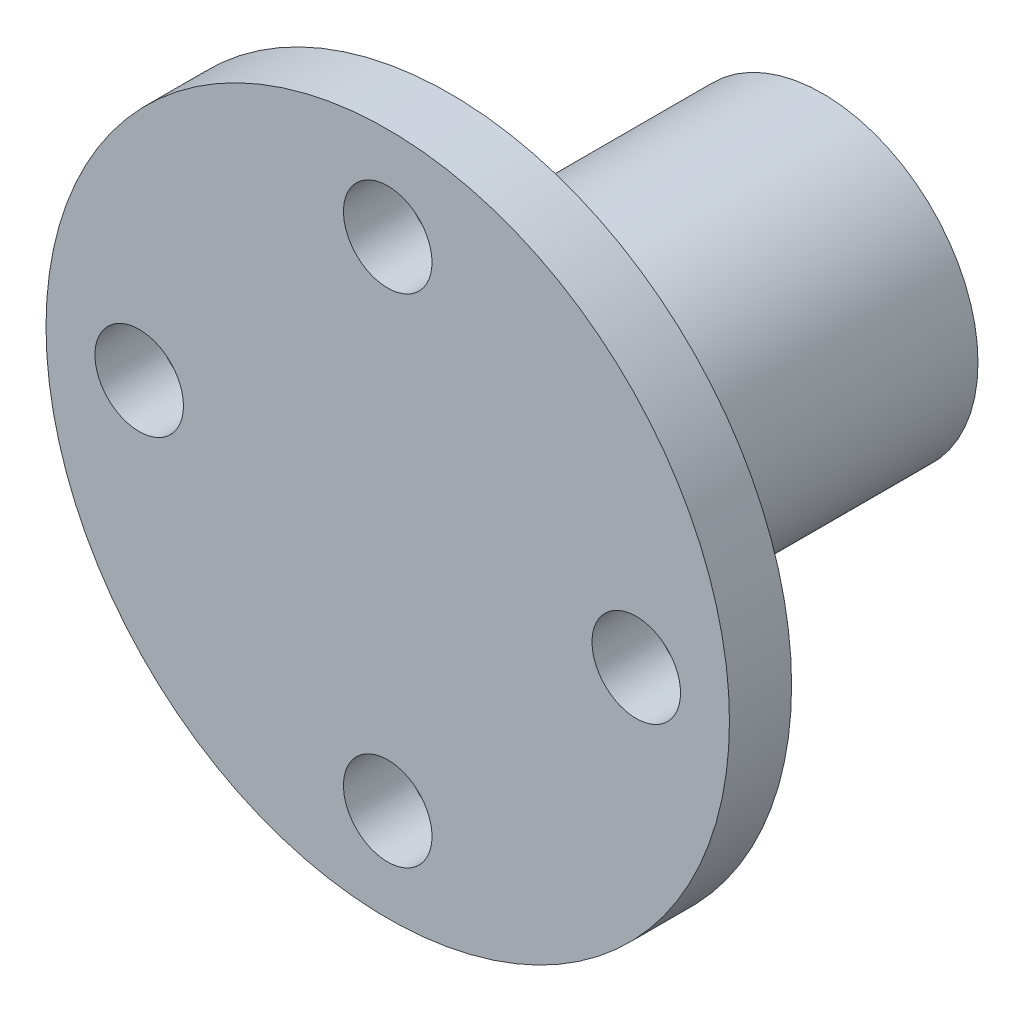
SolidWorks part; units mm, degrees
ref_plane "Front Plane" through (0, 0, 0) normal (0, 0, 1) x (1, 0, 0)
ref_plane "Top Plane" through (0, 0, 0) normal (0, 1, 0) x (1, 0, 0)
ref_plane "Right Plane" through (0, 0, 0) normal (1, 0, 0) x (0, 0, -1)
sketch "Sketch1" plane through (0, 0, 0) normal (0, 0, 1) x (1, 0, 0)
  line L0 (0, 11) -> (0, 5) construction
  circle A0 centre (0, 0) radius 11
  circle A1 centre (0, 0) radius 5
  circle A2 centre (0, 0) radius 1.5
  circle A3 centre (0, 8) radius 1.425
  circle A4 centre (8, 0) radius 1.425
  circle A5 centre (0, -8) radius 1.425
  circle A6 centre (-8, 0) radius 1.425
  point P7 (0, 8)
  point P19 (0, 0)
  dimension "D1" = 22
  dimension "D2" = 10
  dimension "D3" = 3
  dimension "D4" = 2.85
  dimension "D5" = 4
extrude "Boss-Extrude1" add sketch "Sketch1" along normal blind 2 contours A0 A3 A1 A6 A5 A4 | A1 region at (-10.6889, 0, 0)
extrude "Boss-Extrude2" add sketch "Sketch1<4>" against normal blind 12 contours A1 A2 region at (-4.8586, 0, 0)
sketch "Sketch1<4>" plane through (0, 0, 0) normal (0, 0, 1) x (1, 0, 0) same geometry as "Sketch1"
